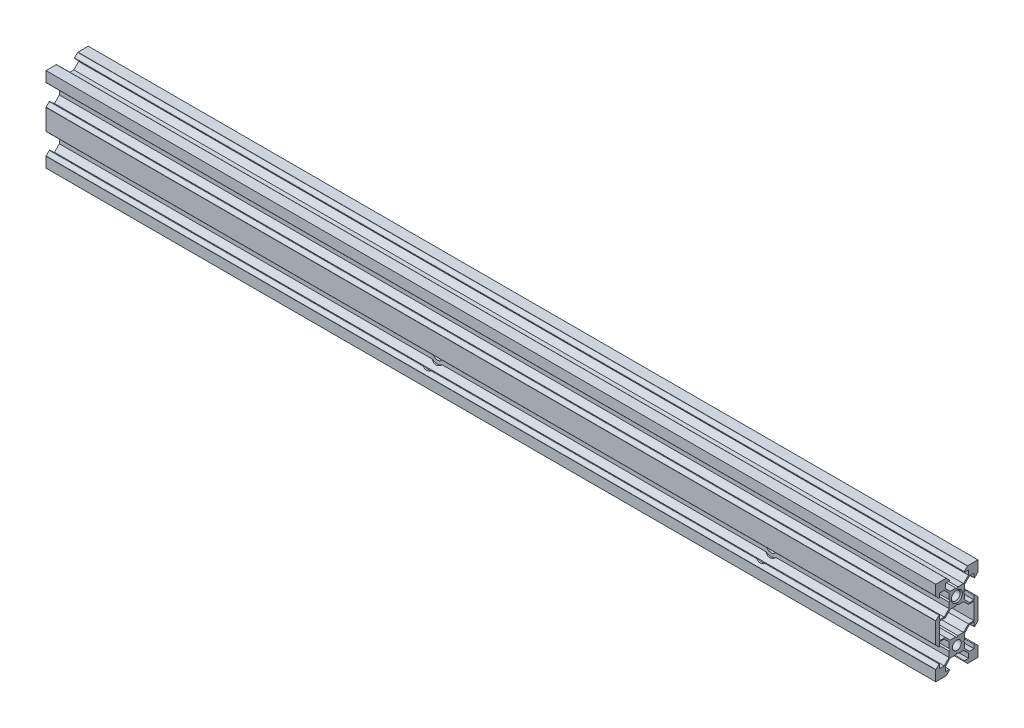
SolidWorks part; units mm, degrees
material "Alloy Steel"
ref_plane "Front Plane" through (0, 0, 0) normal (0, 0, 1) x (1, 0, 0)
ref_plane "Top Plane" through (0, 0, 0) normal (0, 1, 0) x (1, 0, 0)
ref_plane "Right Plane" through (0, 0, 0) normal (1, 0, 0) x (0, 0, -1)
sketch "Sketch2" plane through (0, 0, 0) normal (1, 0, 0) x (0, 0, -1)
  line L0 (0, 2) -> (0, 3) construction
  line L5 (0, 3) -> (-0.5, 3.5)
  line L6 (-0.5, 3.5) -> (-3.01, 3.5)
  line L7 (-3.01, 3.5) -> (-5.2091, 5.6991)
  line L8 (-5.2091, 5.6991) -> (-5.2091, 7.6991)
  line L9 (-5.2091, 7.6991) -> (-3.4791, 7.6991)
  line L10 (-3.4791, 7.6991) -> (-3.4791, 7.8991) construction
  line L11 (-3.4791, 7.8991) -> (-3.3377, 8.0405) construction
  line L12 (-3.3377, 8.0405) -> (-4.7378, 9.4406)
  line L13 (-4.7378, 9.4406) -> (-4.8792, 9.2992) construction
  line L14 (-4.8792, 9.2992) -> (-4.8792, 9.4992) construction
  line L15 (-4.8792, 9.4992) -> (-9.4992, 9.4992)
  line L16 (0, 0) -> (-9.4992, 9.4992) construction
  line L17 (0, 0) -> (-3, 0) construction
  line L18 (-9.4992, 4.8792) -> (-9.4992, 9.4992)
  line L19 (-8.0405, 3.3377) -> (-9.4406, 4.7378)
  line L20 (-7.6991, 5.2091) -> (-7.6991, 3.4791)
  line L21 (-5.6991, 5.2091) -> (-7.6991, 5.2091)
  line L22 (-3.5, 3.01) -> (-5.6991, 5.2091)
  line L23 (-3.5, 0.5) -> (-3.5, 3.01)
  line L24 (-3, 0) -> (-3.5, 0.5)
  line L25 (3, 0) -> (3.5, 0.5)
  line L26 (3.5, 0.5) -> (3.5, 3.01)
  line L27 (3.5, 3.01) -> (5.6991, 5.2091)
  line L28 (5.6991, 5.2091) -> (7.6991, 5.2091)
  line L29 (7.6991, 5.2091) -> (7.6991, 3.4791)
  line L30 (8.0405, 3.3377) -> (9.4406, 4.7378)
  line L31 (9.4992, 4.8792) -> (9.4992, 9.4992)
  line L32 (4.8792, 9.4992) -> (9.4992, 9.4992)
  line L33 (3.3377, 8.0405) -> (4.7378, 9.4406)
  line L34 (5.2091, 7.6991) -> (3.4791, 7.6991)
  line L35 (5.2091, 5.6991) -> (5.2091, 7.6991)
  line L36 (3.01, 3.5) -> (5.2091, 5.6991)
  line L37 (0.5, 3.5) -> (3.01, 3.5)
  line L38 (0, 3) -> (0.5, 3.5)
  line L39 (2, 0) -> (3, 0) construction
  line L40 (7.6991, 3.4791) -> (7.8991, 3.4791) construction
  line L41 (7.8991, 3.4791) -> (8.0405, 3.3377) construction
  line L42 (9.4406, 4.7378) -> (9.2992, 4.8792) construction
  line L43 (9.2992, 4.8792) -> (9.4992, 4.8792) construction
  line L44 (0, 0) -> (9.4992, 9.4992) construction
  line L45 (0, 0) -> (0, 3) construction
  line L46 (0, -3) -> (0.5, -3.5)
  line L47 (0.5, -3.5) -> (3.01, -3.5)
  line L48 (3.01, -3.5) -> (5.2091, -5.6991)
  line L49 (5.2091, -5.6991) -> (7.6991, -5.6991)
  line L50 (7.6991, -5.6991) -> (7.6991, -13.2992)
  line L51 (0, -15.9983) -> (0, -16.8134) construction
  line L52 (7.6991, -13.2992) -> (5.2091, -13.2992)
  line L53 (9.4992, -4.8792) -> (9.4992, -14.1192)
  line L54 (8.0405, -3.3377) -> (9.4406, -4.7378)
  line L55 (7.6991, -5.2091) -> (7.6991, -3.4791)
  line L56 (5.6991, -5.2091) -> (7.6991, -5.2091)
  line L57 (3.5, -3.01) -> (5.6991, -5.2091)
  line L58 (3.5, -0.5) -> (3.5, -3.01)
  line L59 (3, 0) -> (3.5, -0.5)
  line L60 (0, -2) -> (0, -3) construction
  line L61 (-7.6991, -13.2992) -> (-5.2091, -13.2992)
  line L62 (-7.6991, -5.6991) -> (-7.6991, -13.2992)
  line L63 (-5.2091, -5.6991) -> (-7.6991, -5.6991)
  line L65 (0, 0) -> (1.4142, -1.4142) construction
  line L66 (0, 0) -> (3, 0) construction
  line L67 (-3, 0) -> (-3.5, -0.5)
  line L68 (-3.5, -0.5) -> (-3.5, -3.01)
  line L69 (-3.5, -3.01) -> (-5.6991, -5.2091)
  line L70 (-5.6991, -5.2091) -> (-7.6991, -5.2091)
  line L71 (-7.6991, -5.2091) -> (-7.6991, -3.4791)
  line L72 (-8.0405, -3.3377) -> (-9.4406, -4.7378)
  line L73 (-9.4992, -4.8792) -> (-9.4992, -14.1192)
  line L78 (-3.01, -3.5) -> (-5.2091, -5.6991)
  line L79 (-0.5, -3.5) -> (-3.01, -3.5)
  line L80 (0, -3) -> (-0.5, -3.5)
  line L81 (-2, 0) -> (-3, 0) construction
  line L82 (-7.6991, -3.4791) -> (-7.8991, -3.4791) construction
  line L83 (-7.8991, -3.4791) -> (-8.0405, -3.3377) construction
  line L84 (-9.4406, -4.7378) -> (-9.2992, -4.8792) construction
  line L85 (-9.2992, -4.8792) -> (-9.4992, -4.8792) construction
  line L86 (0, 0) -> (-1.4142, -1.4142) construction
  line L87 (0, 0) -> (0, -3) construction
  line L89 (-4.8792, -28.4975) -> (-9.4992, -28.4975)
  line L90 (-3.3377, -27.0389) -> (-4.7378, -28.4389)
  line L91 (-5.2091, -26.6974) -> (-3.4791, -26.6974)
  line L92 (-5.2091, -24.6974) -> (-5.2091, -26.6974)
  line L93 (-9.4992, -23.8775) -> (-9.4992, -28.4975)
  line L94 (-8.0405, -22.336) -> (-9.4406, -23.7361)
  line L95 (-7.6991, -24.2074) -> (-7.6991, -22.4774)
  line L96 (-5.6991, -24.2074) -> (-7.6991, -24.2074)
  line L97 (5.2091, -26.6974) -> (3.4791, -26.6974)
  line L98 (3.3377, -27.0389) -> (4.7378, -28.4389)
  line L99 (4.8792, -28.4975) -> (9.4992, -28.4975)
  line L100 (9.4992, -23.8775) -> (9.4992, -28.4975)
  line L101 (8.0405, -22.336) -> (9.4406, -23.7361)
  line L102 (7.6991, -24.2074) -> (7.6991, -22.4774)
  line L103 (5.6991, -24.2074) -> (7.6991, -24.2074)
  line L104 (5.2091, -24.6974) -> (5.2091, -26.6974)
  line L105 (3.01, -22.4983) -> (5.2091, -24.6974)
  line L106 (3.5, -22.0083) -> (5.6991, -24.2074)
  line L107 (-3.5, -22.0083) -> (-5.6991, -24.2074)
  line L108 (-3.01, -22.4983) -> (-5.2091, -24.6974)
  line L109 (-0.5, -22.4983) -> (-3.01, -22.4983)
  line L110 (0, -21.9983) -> (0.5, -22.4983)
  line L111 (0, -21.9983) -> (-0.5, -22.4983)
  line L112 (0.5, -22.4983) -> (3.01, -22.4983)
  line L113 (3.5, -19.4983) -> (3.5, -22.0083)
  line L114 (-3.5, -19.4983) -> (-3.5, -22.0083)
  line L115 (-3, -18.9983) -> (-3.5, -19.4983)
  line L116 (-3, -18.9983) -> (-3.5, -18.4983)
  line L117 (3, -18.9983) -> (3.5, -19.4983)
  line L118 (3, -18.9983) -> (3.5, -18.4983)
  line L119 (3.5, -18.4983) -> (3.5, -15.9883)
  line L120 (3.01, -15.4983) -> (5.2091, -13.2992)
  line L121 (3.5, -15.9883) -> (5.6991, -13.7892)
  line L122 (5.6991, -13.7892) -> (7.6991, -13.7892)
  line L123 (7.6991, -13.7892) -> (7.6991, -15.5192)
  line L124 (8.0405, -15.6607) -> (9.4406, -14.2606)
  line L128 (-5.6991, -13.7892) -> (-7.6991, -13.7892)
  line L129 (-7.6991, -13.7892) -> (-7.6991, -15.5192)
  line L130 (-8.0405, -15.6607) -> (-9.4406, -14.2606)
  line L134 (-3.01, -15.4983) -> (-5.2091, -13.2992)
  line L135 (-3.5, -15.9883) -> (-5.6991, -13.7892)
  line L136 (-3.5, -18.4983) -> (-3.5, -15.9883)
  line L137 (-0.5, -15.4983) -> (-3.01, -15.4983)
  line L138 (0, -15.9983) -> (-0.5, -15.4983)
  line L139 (0, -15.9983) -> (0.5, -15.4983)
  line L140 (0.5, -15.4983) -> (3.01, -15.4983)
  circle A0 centre (0, 0) radius 2
  arc A1 (-3.3377, 8.0405) -> (-3.4791, 7.6991) centre (-3.4791, 7.8991) cw
  arc A2 (-4.7378, 9.4406) -> (-4.8792, 9.4992) centre (-4.8792, 9.2992) ccw
  arc A3 (-9.4406, 4.7378) -> (-9.4992, 4.8792) centre (-9.2992, 4.8792) cw
  arc A4 (-8.0405, 3.3377) -> (-7.6991, 3.4791) centre (-7.8991, 3.4791) ccw
  arc A5 (8.0405, 3.3377) -> (7.6991, 3.4791) centre (7.8991, 3.4791) cw
  arc A6 (9.4406, 4.7378) -> (9.4992, 4.8792) centre (9.2992, 4.8792) ccw
  arc A7 (4.7378, 9.4406) -> (4.8792, 9.4992) centre (4.8792, 9.2992) cw
  arc A8 (3.3377, 8.0405) -> (3.4791, 7.6991) centre (3.4791, 7.8991) ccw
  arc A11 (9.4406, -4.7378) -> (9.4992, -4.8792) centre (9.2992, -4.8792) cw
  arc A12 (8.0405, -3.3377) -> (7.6991, -3.4791) centre (7.8991, -3.4791) ccw
  arc A13 (-8.0405, -3.3377) -> (-7.6991, -3.4791) centre (-7.8991, -3.4791) cw
  arc A14 (-9.4406, -4.7378) -> (-9.4992, -4.8792) centre (-9.2992, -4.8792) ccw
  arc A17 (-4.7378, -28.4389) -> (-4.8792, -28.4975) centre (-4.8792, -28.2975) cw
  arc A18 (-3.3377, -27.0389) -> (-3.4791, -26.6974) centre (-3.4791, -26.8974) ccw
  arc A19 (-9.4406, -23.7361) -> (-9.4992, -23.8775) centre (-9.2992, -23.8775) ccw
  arc A20 (-8.0405, -22.336) -> (-7.6991, -22.4774) centre (-7.8991, -22.4774) cw
  arc A21 (3.3377, -27.0389) -> (3.4791, -26.6974) centre (3.4791, -26.8974) cw
  arc A22 (4.7378, -28.4389) -> (4.8792, -28.4975) centre (4.8792, -28.2975) ccw
  arc A23 (9.4406, -23.7361) -> (9.4992, -23.8775) centre (9.2992, -23.8775) cw
  arc A24 (8.0405, -22.336) -> (7.6991, -22.4774) centre (7.8991, -22.4774) ccw
  arc A25 (8.0405, -15.6607) -> (7.6991, -15.5192) centre (7.8991, -15.5192) cw
  arc A26 (9.4406, -14.2606) -> (9.4992, -14.1192) centre (9.2992, -14.1192) ccw
  arc A30 (-8.0405, -15.6607) -> (-7.6991, -15.5192) centre (-7.8991, -15.5192) ccw
  arc A31 (-9.4406, -14.2606) -> (-9.4992, -14.1192) centre (-9.2992, -14.1192) cw
  circle A33 centre (0, -18.9983) radius 2
  point P0 (0, 0)
  point P22 (0, 0)
  point P64 (0, 0)
  point P93 (0, 0)
  point P122 (0, 0)
extrude "Main Body" add sketch "Sketch2" along normal blind 200 and the other way blind 200 contours L78 L79 L80 L46 L47 L48 L53 A11 L54 A12 L55 L56 L57 L58 L59 L25 L26 L27 L28 L29 A5 L30 A6 L31 L32 A7 L33 A8 L34 L35 L36 L37 L38 L5 L6 L7 L8 L9 A1 L12 A2 region at (0, 2.9496, -0.5504)
chamfer "Chamfer1" distance 0.5 angle 45 1 edges at (200, 0, -2)
chamfer "Chamfer2" distance 0.5 angle 45 1 edges at (-200, 0, -2)
sketch "Sketch3" plane through (0, 0, 0) normal (0, 0, 1) x (1, 0, 0)
  line L0 (-200, -18.9983) -> (200, -18.9983) construction
  line L1 (-200, -19.4983) -> (-200, -22.0083) construction
  circle A0 centre (-30, -18.9983) radius 2.25
  circle A1 centre (120, -18.9983) radius 2.25
  dimension "D3" = 4.5
  dimension "D4" = 4.5
  dimension "D1" = 170
  dimension "D2" = 320
extrude "Screw Holes" cut sketch "Sketch3" against normal through all both and the other way through all
sketch "Sketch4" plane through (0, 0, 9.4992) normal (0, 0, 1) x (1, 0, 0)
  circle A0 centre (-30, -18.9983) radius 3.75
  circle A1 centre (120, -18.9983) radius 3.75
  dimension "D1" = 7.5
  dimension "D2" = 7.5
extrude "Screw Clearance Hole" cut sketch "Sketch4" against normal up to surface (5.9992 mm away) and the other way through all up to face at (22.5, -17.4333, 3.5)
